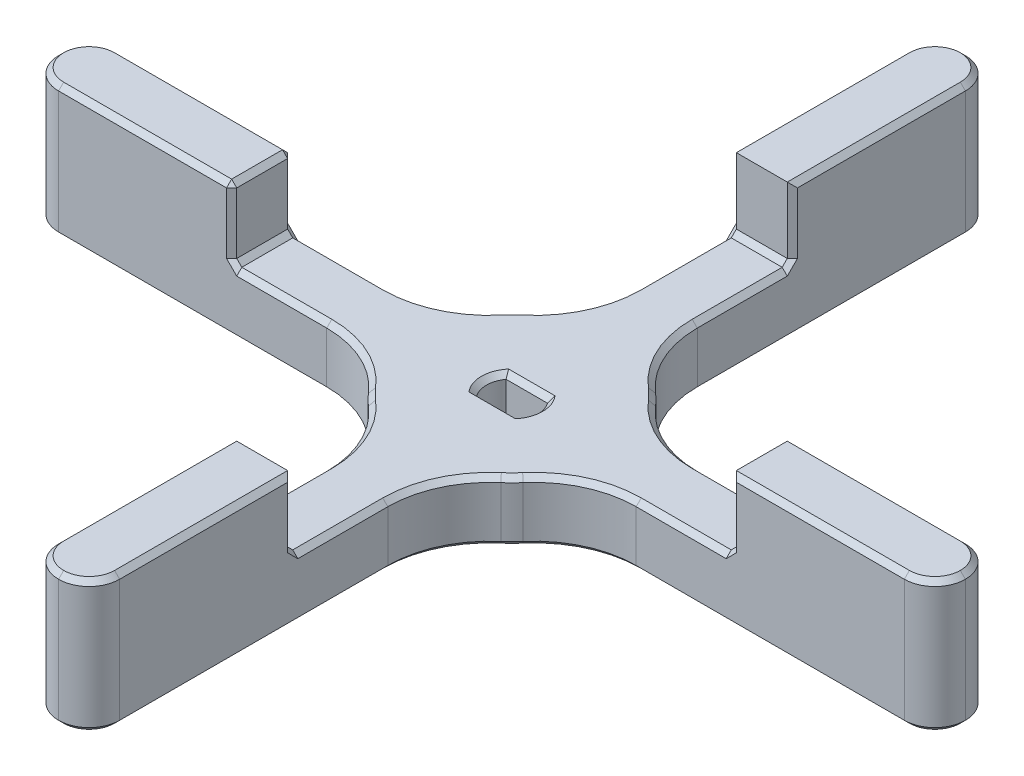
SolidWorks part; units mm, degrees
ref_plane "Front Plane" through (0, 0, 0) normal (0, 0, 1) x (1, 0, 0)
ref_plane "Top Plane" through (0, 0, 0) normal (0, 1, 0) x (1, 0, 0)
ref_plane "Right Plane" through (0, 0, 0) normal (1, 0, 0) x (0, 0, -1)
sketch "Sketch1" plane through (0, 0, 0) normal (0, 1, 0) x (1, 0, 0)
  line L0 (-2.0365, 1.45) -> (2.0365, 1.45)
  line L1 (-2.0365, -1.45) -> (2.0365, -1.45)
  circle A0 centre (0, 0) radius 10
  circle A1 centre (0, 0) radius 2.5
  dimension "D1" = 20
  dimension "D2" = 5
  dimension "D3" = 2.9
  dimension "D4" = 1.45
extrude "Boss-Extrude1" add sketch "Sketch1" along normal blind 6 contours A0 A1 | L0 A1 | L1 A1
sketch "Sketch2" plane through (0, 6, 0) normal (0, 1, 0) x (1, 0, 0)
  line L0 (9.5394, 3) -> (9.5394, -3)
  line L1 (-3, 9.5394) -> (3, 9.5394)
  line L2 (-3, 9.5394) -> (-3, 44.5394)
  line L3 (-3, 44.5394) -> (3, 44.5394)
  line L4 (3, 9.5394) -> (3, 44.5394)
  line L5 (0, 44.5394) -> (0, 9.5394) construction
  line L6 (-3, 27.0394) -> (3, 27.0394) construction
  line L7 (9.5394, 3) -> (44.5394, 3)
  line L8 (44.5394, 3) -> (44.5394, -3)
  line L9 (9.5394, -3) -> (44.5394, -3)
  line L10 (44.5394, 0) -> (9.5394, 0) construction
  line L11 (27.0394, 3) -> (27.0394, -3) construction
  line L12 (3, -9.5394) -> (-3, -9.5394)
  line L13 (3, -9.5394) -> (3, -44.5394)
  line L14 (3, -44.5394) -> (-3, -44.5394)
  line L15 (-3, -9.5394) -> (-3, -44.5394)
  line L16 (0, -44.5394) -> (0, -9.5394) construction
  line L17 (3, -27.0394) -> (-3, -27.0394) construction
  line L18 (-9.5394, -3) -> (-9.5394, 3)
  line L19 (-9.5394, -3) -> (-44.5394, -3)
  line L20 (-44.5394, -3) -> (-44.5394, 3)
  line L21 (-9.5394, 3) -> (-44.5394, 3)
  line L22 (-44.5394, 0) -> (-9.5394, 0) construction
  line L23 (-27.0394, -3) -> (-27.0394, 3) construction
  circle A0 centre (0, 0) radius 10 construction
  point P17 (27.0394, 0)
  point P26 (0, -27.0394)
  point P35 (-27.0394, 0)
  point P36 (0, 0)
  point P352 (0, 27.0394)
  dimension "D1" = 6
  dimension "D2" = 35
  dimension "D3" = 4
extrude "Boss-Extrude2" add sketch "Sketch2" against normal up to surface (6 mm away) up to face at (0, 0, 0)
sketch "Sketch3" plane through (0, 6, 0) normal (0, 1, 0) x (1, 0, 0)
  line L0 (-44.5394, -3) -> (-9.5394, -3) construction
  line L1 (-44.5394, 3) -> (-24.5394, 3)
  line L2 (-44.5394, 3) -> (-44.5394, -3)
  line L3 (-44.5394, -3) -> (-24.5394, -3)
  line L4 (-24.5394, 3) -> (-24.5394, -3)
  line L5 (-34.5394, -3) -> (-34.5394, 3) construction
  line L6 (-44.5394, 0) -> (-24.5394, 0) construction
  line L7 (3, 44.5394) -> (3, 24.5394)
  line L8 (3, 44.5394) -> (-3, 44.5394)
  line L9 (-3, 44.5394) -> (-3, 24.5394)
  line L10 (3, 24.5394) -> (-3, 24.5394)
  line L11 (-3, 34.5394) -> (3, 34.5394) construction
  line L12 (0, 44.5394) -> (0, 24.5394) construction
  line L13 (44.5394, -3) -> (24.5394, -3)
  line L14 (44.5394, -3) -> (44.5394, 3)
  line L15 (44.5394, 3) -> (24.5394, 3)
  line L16 (24.5394, -3) -> (24.5394, 3)
  line L17 (34.5394, 3) -> (34.5394, -3) construction
  line L18 (44.5394, 0) -> (24.5394, 0) construction
  line L19 (-3, -44.5394) -> (-3, -24.5394)
  line L20 (-3, -44.5394) -> (3, -44.5394)
  line L21 (3, -44.5394) -> (3, -24.5394)
  line L22 (-3, -24.5394) -> (3, -24.5394)
  line L23 (3, -34.5394) -> (-3, -34.5394) construction
  line L24 (0, -44.5394) -> (0, -24.5394) construction
  point P17 (0, 34.5394)
  point P26 (34.5394, 0)
  point P35 (0, -34.5394)
  point P36 (0, 0)
  point P196 (-34.5394, 0)
  dimension "D1" = 20
extrude "Boss-Extrude3" add sketch "Sketch3" along normal blind 7
fillet "Fillet1" radius 10 8 edges at (9.5394, 3, -3) (-9.5394, 3, -3) (3, 3, -9.5394) (3, 3, 9.5394) (-3, 3, -9.5394) (-3, 3, 9.5394) (9.5394, 3, 3) (-9.5394, 3, 3)
fillet "Fillet2" radius 3 8 edges at (44.5394, 6.5, -3) (44.5394, 6.5, 3) (3, 6.5, 44.5394) (-3, 6.5, 44.5394) (-44.5394, 6.5, 3) (-44.5394, 6.5, -3) (3, 6.5, -44.5394) (-3, 6.5, -44.5394)
chamfer "Chamfer1" distance 0.5 angle 45 85 edges at (19.869, 6, -3) (24.5394, 6, 0) (24.5394, 9.5, -3) (24.5394, 9.5, 3) (33.0394, 13, 3) (0, 6, 1.45) (3, 6, 19.869) (0, 6, 24.5394) (3, 9.5, 24.5394) (-3, 9.5, 24.5394) (-3, 13, 33.0394) (28.369, 0, -3) (7.0711, 6, -7.0711) (7.0711, 0, -7.0711) (3, 6, -19.869) (-3, 0, -28.369) (-7.0711, 0, -7.0711) (-7.0711, 6, -7.0711) (-19.869, 6, -3) (-28.369, 0, 3) (-7.0711, 6, 7.0711) (-7.0711, 0, 7.0711) (-3, 6, 19.869) (3, 0, 28.369) (7.0711, 6, 7.0711) (7.0711, 0, 7.0711) (19.869, 6, 3) (11.0154, 6, -3.917) (11.0154, 0, -3.917) (3.917, 6, -11.0154) (3.917, 0, -11.0154) (-3.917, 6, -11.0154) (-3.917, 0, -11.0154) (-2.5, 6, 0) (-11.0154, 6, -3.917) (-11.0154, 0, -3.917) (-11.0154, 6, 3.917) (-11.0154, 0, 3.917) (-3.917, 6, 11.0154) (-3.917, 0, 11.0154) (3.917, 6, 11.0154) (3.917, 0, 11.0154) (11.0154, 6, 3.917) (11.0154, 0, 3.917) (0, 6, -1.45) (33.0394, 13, -3) (43.6607, 13, 2.1213) (43.6607, 13, -2.1213) (-28.369, 0, -3) (3, 0, -28.369) (28.369, 0, 3) (-3, 0, 28.369) (-2.1213, 0, -43.6607) (2.1213, 0, -43.6607) (-43.6607, 0, -2.1213) (-43.6607, 0, 2.1213) (-2.1213, 0, 43.6607) (2.1213, 0, 43.6607) (43.6607, 0, 2.1213) (43.6607, 0, -2.1213) (3, 13, 33.0394) (-2.1213, 13, 43.6607) (2.1213, 13, 43.6607) (-33.0394, 13, 3) (-43.6607, 13, -2.1213) (-43.6607, 13, 2.1213) (-3, 13, -33.0394) (-2.1213, 13, -43.6607) (2.1213, 13, -43.6607) (2.5, 6, 0) (0, 0, -1.45) (-2.5, 0, 0) (0, 0, 1.45) (-19.869, 6, 3) (-24.5394, 6, 0) (-24.5394, 9.5, 3) (-24.5394, 9.5, -3) (2.5, 0, 0) (-24.5394, 13, 0) (-33.0394, 13, -3) (-3, 6, -19.869) (0, 6, -24.5394) (-3, 9.5, -24.5394) (3, 9.5, -24.5394) (3, 13, -33.0394)
